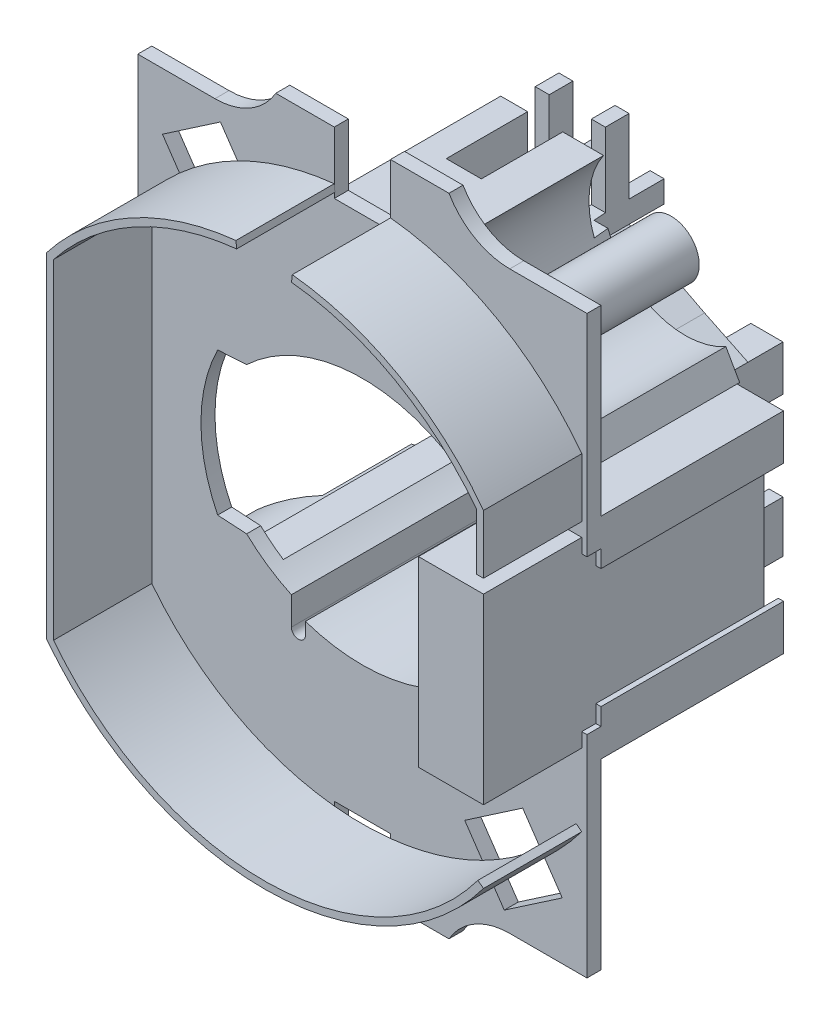
SolidWorks part; units mm, degrees
ref_plane "Face" through (0, 0, 0) normal (0, 0, 1) x (1, 0, 0)
ref_plane "Dessus" through (0, 0, 0) normal (0, 1, 0) x (1, 0, 0)
ref_plane "Droite" through (0, 0, 0) normal (1, 0, 0) x (0, 0, -1)
sketch "Esquisse1" plane through (0, 0, 0) normal (0, 0, 1) x (1, 0, 0)
  line L0 (0, 0) -> (26.1559, 0) construction
  line L1 (0, 0) -> (0, 34.5794) construction
  line L2 (16, -20.5) -> (16, 20.5) construction
  line L3 (16, 20.5) -> (10.5, 20.5) construction
  line L4 (6.1699, 23) -> (2, 23) construction
  line L5 (16, -20.5) -> (16, -5.4838)
  line L6 (16, 20.5) -> (10.5, 20.5)
  line L7 (6.1699, 23) -> (2, 23)
  line L8 (2, 23) -> (2, 18.5949)
  line L9 (3.7648, 18.5949) -> (-3.7951, 18.5949) construction
  line L10 (2, 18.5949) -> (-2, 18.5949)
  line L11 (11, 6.5) -> (11, -6.5)
  line L12 (11, 6.5) -> (15.6298, 6.5)
  line L13 (5.224, -8.0659) -> (5.224, -9.3934)
  line L14 (15.6298, 6.5) -> (15.6298, 5.4838)
  line L15 (15.6298, 5.4838) -> (16, 5.4838)
  line L16 (16, 5.4838) -> (16, 20.5)
  line L17 (10.5, 4.6904) -> (10.5, -4.6904)
  line L18 (0, 0) -> (0, -19.2662) construction
  line L19 (0, 26) -> (0, 24) construction
  line L20 (-8.2443, 5.2196) -> (-10.309, 5.0966)
  line L21 (8.2443, 5.2196) -> (10.309, 5.0966)
  line L22 (16, -20.5) -> (10.5, -20.5)
  line L23 (-8.2443, -5.2196) -> (-10.309, -5.0966)
  line L24 (15.6298, -5.4838) -> (16, -5.4838)
  line L25 (15.6298, -6.5) -> (15.6298, -5.4838)
  line L26 (11, -6.5) -> (15.6298, -6.5)
  line L27 (-4.0566, -8.5251) -> (-4.0566, -9.3826)
  line L28 (-5.0566, -7.3826) -> (-5.0566, -9.3826)
  line L29 (6.1699, -23) -> (2, -23)
  line L30 (2, -23) -> (2, -18.5949)
  line L31 (2, -18.5949) -> (-2, -18.5949)
  line L32 (-16, -20.5) -> (-10.5, -20.5) construction
  line L33 (-2, 23) -> (-6.1699, 23) construction
  line L34 (-16, 20.5) -> (-16, -20.5) construction
  line L35 (-10.5, 20.5) -> (-16, 20.5) construction
  line L36 (-16, -20.5) -> (-10.5, -20.5)
  line L37 (-2, 23) -> (-6.1699, 23)
  line L38 (-16, 20.5) -> (-16, -20.5)
  line L39 (-10.5, 20.5) -> (-16, 20.5)
  line L41 (-6.1699, -23) -> (-2, -23)
  line L42 (-2, 23) -> (-2, 18.5949)
  line L43 (-2, -23) -> (-2, -18.5949)
  line L44 (0, 0) -> (-12.6849, 18.5949) construction
  line L45 (-14.2403, 16.4387) -> (-10.1099, 19.2564)
  line L46 (-10.1099, 19.2564) -> (-7.2922, 15.1259)
  line L47 (-7.2922, 15.1259) -> (-11.4226, 12.3082)
  line L48 (-14.2403, 16.4387) -> (-11.4226, 12.3082)
  line L49 (0, 0) -> (29.6565, 20.2308) construction
  line L50 (10.1099, -19.2564) -> (14.2403, -16.4387)
  line L51 (14.2403, -16.4387) -> (11.4226, -12.3082)
  line L52 (11.4226, -12.3082) -> (7.2922, -15.1259)
  line L53 (10.1099, -19.2564) -> (7.2922, -15.1259)
  arc A0 (6.1699, 23) -> (10.5, 20.5) centre (10.5, 25.5) ccw construction
  arc A1 (6.1699, 23) -> (10.5, 20.5) centre (10.5, 25.5) ccw
  arc A2 (10.5, 4.6904) -> (10.309, 5.0966) centre (0, 0) ccw
  arc A3 (10.309, -5.0966) -> (10.5, -4.6904) centre (0, 0) ccw
  arc A4 (8.2443, 5.2196) -> (-8.2443, 5.2196) centre (0, -3.5) ccw
  arc A5 (6.1699, -23) -> (10.5, -20.5) centre (10.5, -25.5) cw
  arc A6 (-10.309, 5.0966) -> (-10.309, -5.0966) centre (0, 0) ccw
  arc A7 (-5.0566, -9.3826) -> (-4.0566, -9.3826) centre (-4.5566, -9.3826) ccw
  arc A8 (-5.0566, -7.3826) -> (-8.2443, -5.2196) centre (0, 3.5) cw
  arc A9 (5.9841, -9.8204) -> (5.224, -9.3934) centre (5.724, -9.3934) cw
  arc A10 (5.224, -8.0659) -> (-4.0566, -8.5251) centre (0, 3.5) cw
  arc A11 (-6.1699, -23) -> (-10.5, -20.5) centre (-10.5, -25.5) ccw construction
  arc A12 (-10.5, 20.5) -> (-6.1699, 23) centre (-10.5, 25.5) ccw construction
  arc A13 (-6.1699, -23) -> (-10.5, -20.5) centre (-10.5, -25.5) ccw
  arc A14 (-10.5, 20.5) -> (-6.1699, 23) centre (-10.5, 25.5) ccw
  arc A16 (5.9841, -9.8204) -> (10.309, -5.0966) centre (0, 0) ccw
  point P15 (0, -8.5)
  point P30 (0, 8.5)
  point P42 (10.5, 0)
  point P46 (11, 0)
  point P66 (0, 18.5949)
  point P67 (0, -18.5949)
  point P73 (-9.3574, 13.7171)
  point P74 (-12.1751, 17.8475)
  point P77 (12.1751, -17.8475)
  dimension "D2" = 6.5
  dimension "D4" = 12
  dimension "D6" = 23
  dimension "D7" = 0.5
  dimension "D1" = 5
  dimension "D5" = 8.5
  dimension "D8" = 1
  dimension "D9" = 5
  dimension "D10" = 5
  dimension "D3" = 0.5
extrude "Base-Extrusion" add sketch "Esquisse1" along normal blind 1
sketch "Esquisse2" plane through (0, 0, 1) normal (0, 0, 1) x (1, 0, 0)
  line L0 (15.1298, 7.4724) -> (15.1298, 11.493)
  line L1 (2.0067, 19.3965) -> (1.9553, 18.8991)
  line L2 (-15.5, 12) -> (-15.5, -11.8322)
  line L3 (-2.0067, 19.4993) -> (-1.9555, 19.0019)
  line L4 (15.2291, -11.3611) -> (15.6298, -11.6601)
  line L6 (15.6298, 7.4724) -> (15.1298, 7.4724)
  line L10 (-15, 11.8278) -> (-15, -11.6619)
  line L12 (15.6298, 7.4724) -> (15.6298, 11.6601)
  arc A1 (-1.9555, 19.0019) -> (-15, 11.8278) centre (0, 0) ccw
  arc A3 (-15, -11.6619) -> (15.2291, -11.3611) centre (0, 0) ccw
  arc A4 (15.6298, 11.6601) -> (2.0067, 19.3965) centre (0, 0) ccw
  arc A5 (15.1298, 11.493) -> (1.9553, 18.8991) centre (0, 0) ccw
  arc A6 (-2.0067, 19.4993) -> (-15.5, 12) centre (0, 0) ccw
  arc A7 (-15.5, -11.8322) -> (15.6298, -11.6601) centre (0, 0) ccw
  dimension "D1" = 0.5
  dimension "D4" = 19.5
  dimension "D2" = 0.5
  dimension "D3" = 15.5
  dimension "D5" = 0.5
  dimension "D6" = 0.5
  dimension "D7" = 0.5
extrude "Boss.-Extru.1" add sketch "Esquisse2" along normal blind 7
sketch "Esquisse3" plane through (0, 0, 0) normal (0, 0, -1) x (-1, 0, 0)
  circle A0 centre (-9, 14.5) radius 2
  circle A2 centre (9, -14.5) radius 2
  dimension "D1" = 14.5
  dimension "D2" = 14.5
  dimension "D3" = 9
  dimension "D4" = 9
extrude "Boss.-Extru.2" add sketch "Esquisse3" along normal blind 12
sketch "Esquisse4" plane through (0, 0, 0) normal (0, 0, -1) x (-1, 0, 0)
  line L0 (-15.6298, 6.5) -> (-15.6298, 5.4838) construction
  line L1 (-16, 5.4838) -> (-16, 20.5) construction
  line L2 (-16, -20.5) -> (-16, -5.4838) construction
  line L3 (-15.6298, -5.4838) -> (-15.6298, -6.5) construction
  line L4 (-15.6298, -6.5) -> (-11, -6.5) construction
  line L5 (-11, -6.5) -> (-11, 6.5) construction
  line L6 (-11, 6.5) -> (-15.6298, 6.5) construction
  line L9 (-5.224, -8.0659) -> (-5.224, -9.3934) construction
  line L10 (4.0566, -9.3826) -> (4.0566, -8.5251) construction
  line L11 (5.0566, -7.3826) -> (5.0566, -9.3826) construction
  line L14 (-15.6298, 6.5) -> (-15.6298, 4.2559)
  line L15 (-16, 4.2559) -> (-16, 7.4908)
  line L16 (-16, -7.4908) -> (-16, -4.2559)
  line L17 (-15.6298, -4.2559) -> (-15.6298, -6.5)
  line L18 (-15.6298, -6.5) -> (-11, -6.5)
  line L19 (-11, -6.5) -> (-11, 6.5)
  line L20 (-11, 6.5) -> (-15.6298, 6.5)
  line L21 (-8.2443, 5.2196) -> (-8.2443, -8.0176)
  line L22 (3.1426, -14.5) -> (3.1426, -17.8378)
  line L23 (-5.224, -8.0659) -> (-5.224, -9.3934)
  line L24 (4.0566, -9.3826) -> (4.0566, -8.5251)
  line L25 (5.0566, -7.3826) -> (5.0566, -9.3826)
  line L26 (-10.9111, -7.4908) -> (-3.1426, -13.6994)
  line L27 (-11.8945, 9.4047) -> (-12.8766, 7.6759)
  line L28 (0, 0) -> (-20.4495, 0) construction
  line L29 (-16, 4.2559) -> (-15.6298, 4.2559)
  line L30 (-16, -4.2559) -> (-15.6298, -4.2559)
  line L31 (-16, -7.4908) -> (-10.9111, -7.4908)
  line L33 (-3.1426, -13.6994) -> (-3.1426, -17.8378)
  line L34 (-3.1426, -17.8378) -> (3.1426, -17.8378)
  line L35 (0, 0) -> (0, -18.9364) construction
  line L37 (12.8289, -10.0673) -> (13.3258, -9.1792)
  line L38 (6.6332, -6.5) -> (9, -6.5)
  line L39 (9, -6.5) -> (9, -7.6426)
  line L40 (-4.1835, 17.8378) -> (3.1426, 17.8378)
  line L43 (-16, 7.4908) -> (-12.531, 7.4908)
  line L44 (4.3067, 9.8211) -> (3.1426, 17.8378)
  line L45 (9.6184, 6.6729) -> (8.2443, 5.2196)
  arc A0 (-10.5, -4.6904) -> (-5.9841, -9.8204) centre (0, 0) ccw construction
  arc A1 (-5.9841, -9.8204) -> (-5.224, -9.3934) centre (-5.724, -9.3934) ccw construction
  arc A2 (-5.224, -8.0659) -> (4.0566, -8.5251) centre (0, 3.5) ccw construction
  arc A3 (4.0566, -9.3826) -> (5.0566, -9.3826) centre (4.5566, -9.3826) ccw construction
  arc A4 (5.0566, -7.3826) -> (8.2443, -5.2196) centre (0, 3.5) ccw construction
  arc A6 (8.2443, 5.2196) -> (-8.2443, 5.2196) centre (0, -3.5) ccw construction
  arc A7 (-8.2443, -8.0176) -> (-5.9841, -9.8204) centre (0, 0) ccw
  arc A8 (-5.9841, -9.8204) -> (-5.224, -9.3934) centre (-5.724, -9.3934) ccw
  arc A9 (-5.224, -8.0659) -> (4.0566, -8.5251) centre (0, 3.5) ccw
  arc A10 (4.0566, -9.3826) -> (5.0566, -9.3826) centre (4.5566, -9.3826) ccw
  arc A11 (5.0566, -7.3826) -> (6.6332, -6.5) centre (0, 3.5) ccw
  arc A12 (9.6184, 6.6729) -> (4.3067, 9.8211) centre (0, -3.5) ccw
  arc A13 (8.2443, 5.2196) -> (-8.2443, 5.2196) centre (0, -3.5) ccw
  arc A15 (-12.8766, 7.6759) -> (-12.531, 7.4908) centre (-9, 14.5) ccw
  arc A16 (12.8289, -10.0673) -> (3.1426, -14.5) centre (9, -14.5) ccw
  arc A17 (13.3258, -9.1792) -> (9, -7.6426) centre (9, -14.5) ccw
  arc A18 (-11.8945, 9.4047) -> (-4.1835, 17.8378) centre (-9, 14.5) ccw
  circle A19 centre (-9, 14.5) radius 2 construction
  circle A20 centre (9, -14.5) radius 2 construction
  point P42 (0, -17.8378)
  dimension "D2" = 5.8574
  dimension "D3" = 2
  dimension "D4" = 5.86
  dimension "D1" = 1
extrude "Boss.-Extru.3" add sketch "Esquisse4" along normal blind 13
ref_plane "Plan1" through (0, 0, -12) normal (0, 0, -1) x (-1, 0, 0)
sketch "Esquisse6" plane through (0, 0, -12) normal (0, 0, -1) x (-1, 0, 0)
  line L0 (-11, 6.5) -> (-15.6298, 6.5) construction
  line L1 (-11, 6.5) -> (-15.6298, 6.5)
  line L2 (-11, -6.5) -> (-11, 6.5) construction
  line L3 (-11, -6.5) -> (-11, 6.5)
  line L4 (-15.6298, -6.5) -> (-11, -6.5) construction
  line L5 (-15.6298, -6.5) -> (-11, -6.5)
  line L6 (-15.6298, -5.4838) -> (-15.6298, -6.5) construction
  line L7 (-15.6298, 6.5) -> (-15.6298, -6.5)
extrude "Boss.-Extru.4" add sketch "Esquisse6" against normal blind 20
sketch "Esquisse7" plane through (0, 0, 0) normal (0, 0, -1) x (-1, 0, 0)
  line L0 (-3.5959, -12.9023) -> (-10.9687, -6.5)
  line L1 (-11, -6.5) -> (-15.6298, -6.5) construction
  line L2 (-10.9687, -6.5) -> (-10.9687, 6.7251)
  line L3 (-10.9687, 6.7251) -> (-7.8801, 8.2196)
  line L4 (-7.8801, 8.2196) -> (-2.5, 11)
  line L5 (-2.5, 11) -> (-2.5, 17.8378)
  line L6 (3.1426, 17.8378) -> (-4.1835, 17.8378) construction
  dimension "D1" = 2.5
extrude "Boss.-Extru.-Mince1" add sketch "Esquisse7" along normal blind 18 thin
sketch "Esquisse8" plane through (0, 0, 0) normal (0, 0, -1) x (-1, 0, 0)
  line L0 (0, 0) -> (0, 22.9651) construction
  line L2 (-2.5, 12.3473) -> (-2.5, 17.8378) construction
  line L5 (2.5, 12.3473) -> (7.5274, 7.4765)
  line L8 (2.5, 12.3473) -> (2.5, 17.8378)
  dimension "D1" = 7
extrude "Boss.-Extru.-Mince2" add sketch "Esquisse8" along normal blind 18 thin
sketch "Esquisse9" plane through (10.9687, 0, 0) normal (1, 0, 0) x (0, 0, -1)
  line L0 (-1, 3.5) -> (0, 3.5) construction
  line L1 (18, 3.5) -> (12, 3.5)
  line L2 (18, 3.5) -> (18, -2.8395)
  line L3 (18, -2.8395) -> (12, -2.8395)
  line L4 (12, 3.5) -> (12, -2.8395)
  line L5 (12, -7.1034) -> (12, 7.1034) construction
  line L6 (18, -6.5) -> (18, 6.7251) construction
extrude "Enlèv. mat.-Extru.1" cut sketch "Esquisse9" against normal blind 18
sketch "Esquisse10" plane through (0, 17.8378, 0) normal (0, 1, 0) x (-1, 0, 0)
  line L1 (-1.2769, -6.2011) -> (1.2248, -6.2011)
  line L3 (1.5, -13) -> (-1.5, -13) construction
  line L4 (1.2248, -13) -> (-1.2769, -13)
  line L5 (-1.2769, -6.2011) -> (-1.2769, -13)
  line L6 (1.2248, -6.2011) -> (1.2248, -13)
extrude "Enlèv. mat.-Extru.2" cut sketch "Esquisse10" against normal blind 48
sketch "Esquisse11" plane through (0, 0, 0) normal (1, 0, 0) x (0, 0, -1)
  line L0 (18, 6.7251) -> (13, 6.7251) construction
  line L1 (15.5, -6.8065) -> (18.8365, -6.8065)
  line L2 (15.5, 19.6967) -> (15.5, 12.5599)
  line L3 (15.5, 12.5599) -> (18.8365, 12.5599)
  line L4 (15.5, -12.9023) -> (19.2868, -12.9023)
  line L5 (18.8365, 11) -> (15.5, 11)
  line L6 (15.5, -6.8065) -> (15.5, -12.9023)
  line L7 (18.8365, 6.7251) -> (15.5, 6.7251)
  line L8 (15.5, 11) -> (15.5, 6.7251)
  line L9 (18, 11) -> (13, 11) construction
  line L10 (18.8365, 11) -> (18.8365, 12.5599)
  line L11 (19.2868, 21.6222) -> (19.2868, -12.9023)
  line L12 (13.8128, 19.6967) -> (13.8128, 12.5599)
  line L14 (18, -12.9023) -> (13, -12.9023) construction
  line L16 (18.8365, 6.7251) -> (18.8365, -6.8065)
  line L17 (13.8128, 12.5599) -> (12, 12.4194)
  line L18 (12, -7.1034) -> (12, 7.1034) construction
  line L19 (12, 12.4194) -> (12, 21.6222)
  line L20 (13.8128, 19.6967) -> (15.5, 19.6967)
  line L21 (12, 21.6222) -> (19.2868, 21.6222)
extrude "Enlèv. mat.-Extru.3" cut sketch "Esquisse11" against normal mid plane 48
sketch "Esquisse12" plane through (0, 0, 0) normal (0, 1, 0) x (1, 0, 0)
  line L1 (-15.2693, 16.8967) -> (-10.5, 16.8967)
  line L2 (-15.2693, 16.8967) -> (-15.2693, 3.5311)
  line L4 (-10.5, 16.8967) -> (-10.5, 6.6613)
  line L5 (-15.2693, 3.5311) -> (-10.5, 6.6613)
extrude "Enlèv. mat.-Extru.4" cut sketch "Esquisse12" against normal blind 13
